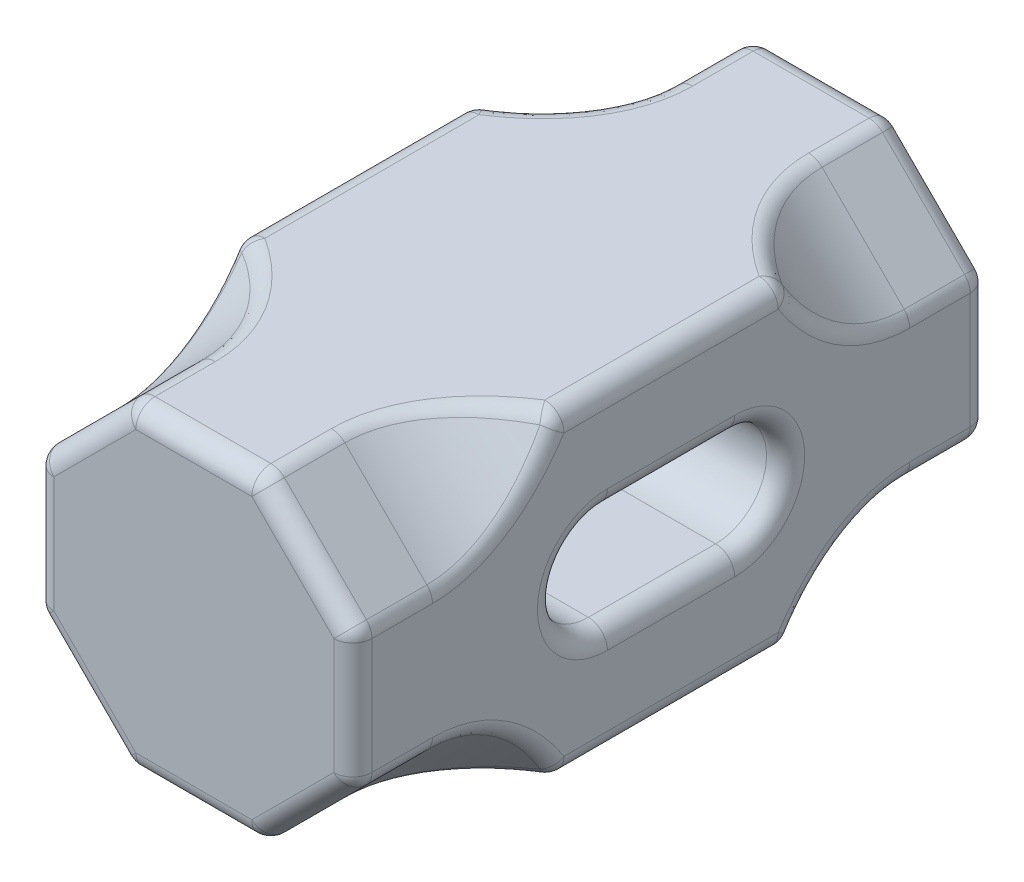
SolidWorks part; units mm, degrees
ref_plane "Front Plane" through (0, 0, 0) normal (0, 0, 1) x (1, 0, 0)
ref_plane "Top Plane" through (0, 0, 0) normal (0, 1, 0) x (1, 0, 0)
ref_plane "Right Plane" through (0, 0, 0) normal (1, 0, 0) x (0, 0, -1)
sketch "Sketch2" plane through (0, 0, 0) normal (0, 0, 1) x (1, 0, 0)
  line L1 (-25, -25) -> (25, -25)
  line L2 (-25, -25) -> (-25, 25)
  line L3 (-25, 25) -> (25, 25)
  line L4 (25, -25) -> (25, 25)
  line L5 (-25, -25) -> (25, 25) construction
  line L6 (-25, 25) -> (25, -25) construction
  point P0 (0, 0)
  dimension "D1" = 50
extrude "Boss-Extrude3" add sketch "Sketch2" along normal mid plane 100
sketch "Sketch3" plane through (0, 0, 50) normal (0, 0, 1) x (1, 0, 0)
  line L0 (25, -25) -> (25, 25) construction
  line L1 (25, 10.3553) -> (10.3553, 25)
  line L2 (10.3553, 25) -> (-10.3553, 25)
  line L3 (-10.3553, 25) -> (-25, 10.3553)
  line L4 (-25, 10.3553) -> (-25, -10.3553)
  line L5 (-25, -10.3553) -> (-10.3553, -25)
  line L6 (-10.3553, -25) -> (10.3553, -25)
  line L7 (10.3553, -25) -> (25, -10.3553)
  line L8 (25, -10.3553) -> (25, 10.3553)
  line L13 (25, -25) -> (25, 25)
  line L14 (25, 25) -> (-25, 25)
  line L15 (-25, 25) -> (-25, -25)
  line L16 (-25, -25) -> (25, -25)
  line L17 (25, -25) -> (25, 25)
  line L18 (25, 25) -> (-25, 25)
  line L19 (-25, 25) -> (-25, -25)
  line L20 (-25, -25) -> (25, -25)
  circle A0 centre (0, 0) radius 25 construction
  line M6 (25, -25) -> (25, 25)
  line M7 (25, 25) -> (-25, 25)
  line M8 (-25, 25) -> (-25, -25)
  line M9 (-25, -25) -> (25, -25)
  dimension "D1" = 0
extrude "Cut-Extrude1" cut sketch "Sketch3" against normal blind 12.5 contours L1 M6 M7 | L3 M7 M8 | L5 M8 M9 | L7 M9 M6 region at (20.1184, 20.1184, 50) region at (20.1184, -20.1184, 50) region at (-20.1184, 20.1184, 50) region at (-20.1184, -20.1184, 50)
sketch "Sketch4" plane through (-17.6777, 17.6777, 0) normal (-0.7071, 0.7071, 0) x (0, 0, 1)
  line L0 (37.5, 25) -> (50, 25) construction
  circle A0 centre (37.5, 50) radius 25
  dimension "D1" = 50
extrude "Cut-Extrude2" cut sketch "Sketch4" against normal through all both and the other way through all
pattern_circular "CirPattern1" count 4 over 360 about axis through (0, 0, 50) along (0, 0, 1) of "Cut-Extrude2"
ref_plane "Plane1" through (0, 0, 0) normal (0, 0, 1) x (1, 0, 0)
mirror "Mirror1" about plane through (0, 0, 0) normal (0, 0, 1) of "CirPattern1", "Cut-Extrude2", "Cut-Extrude1"
sketch "Sketch5" plane through (25, 0, 0) normal (1, 0, 0) x (0, 0, -1)
  line L0 (0, 25) -> (0, -25) construction
  line L1 (-17.2384, 25) -> (17.2384, 25) construction
  line L2 (-17.2384, -25) -> (17.2384, -25) construction
  line L3 (-10, 0) -> (10, 0) construction
  line L4 (-10, 8) -> (10, 8)
  line L5 (-10, -8) -> (10, -8)
  arc A0 (-10, 8) -> (-10, -8) centre (-10, 0) ccw
  arc A1 (10, -8) -> (10, 8) centre (10, 0) ccw
  point P8 (0, 0)
  dimension "D1" = 20
  dimension "D2" = 16
extrude "Cut-Extrude3" cut sketch "Sketch5" against normal through all both and the other way through all
fillet "Fillet1" radius 3 60 edges at (-25, 0, 18) (-25, -8, 0) (-25, 0, -18) (-25, 8, 0) (25, -8, 0) (25, 0, -18) (25, 8, 0) (25, 0, 18) (14.2287, -25, -26.1228) (25, -14.2287, -26.1228) (-14.2287, -25, -26.1228) (-25, -14.2287, -26.1228) (-25, 14.2287, -26.1228) (-14.2287, 25, -26.1228) (14.2287, 25, -26.1228) (25, 14.2287, -26.1228) (17.6777, -17.6777, -50) (25, -10.3553, -43.75) (10.3553, -25, -43.75) (-17.6777, -17.6777, -50) (-10.3553, -25, -43.75) (-25, -10.3553, -43.75) (-17.6777, 17.6777, -50) (-25, 10.3553, -43.75) (-10.3553, 25, -43.75) (17.6777, 17.6777, -50) (10.3553, 25, -43.75) (25, 10.3553, -43.75) (14.2287, -25, 26.1228) (25, -14.2287, 26.1228) (-14.2287, -25, 26.1228) (-25, -14.2287, 26.1228) (-25, 14.2287, 26.1228) (-14.2287, 25, 26.1228) (14.2287, 25, 26.1228) (25, 14.2287, 26.1228) (17.6777, -17.6777, 50) (10.3553, -25, 43.75) (25, -10.3553, 43.75) (-17.6777, -17.6777, 50) (-25, -10.3553, 43.75) (-10.3553, -25, 43.75) (-17.6777, 17.6777, 50) (-10.3553, 25, 43.75) (-25, 10.3553, 43.75) (17.6777, 17.6777, 50) (25, 10.3553, 43.75) (10.3553, 25, 43.75) (25, 0, -50) (0, 25, -50) (-25, 0, -50) (0, -25, -50) (25, 0, 50) (0, 25, 50) (-25, 0, 50) (0, -25, 50) (25, -25, 0) (-25, -25, 0) (-25, 25, 0) (25, 25, 0)
